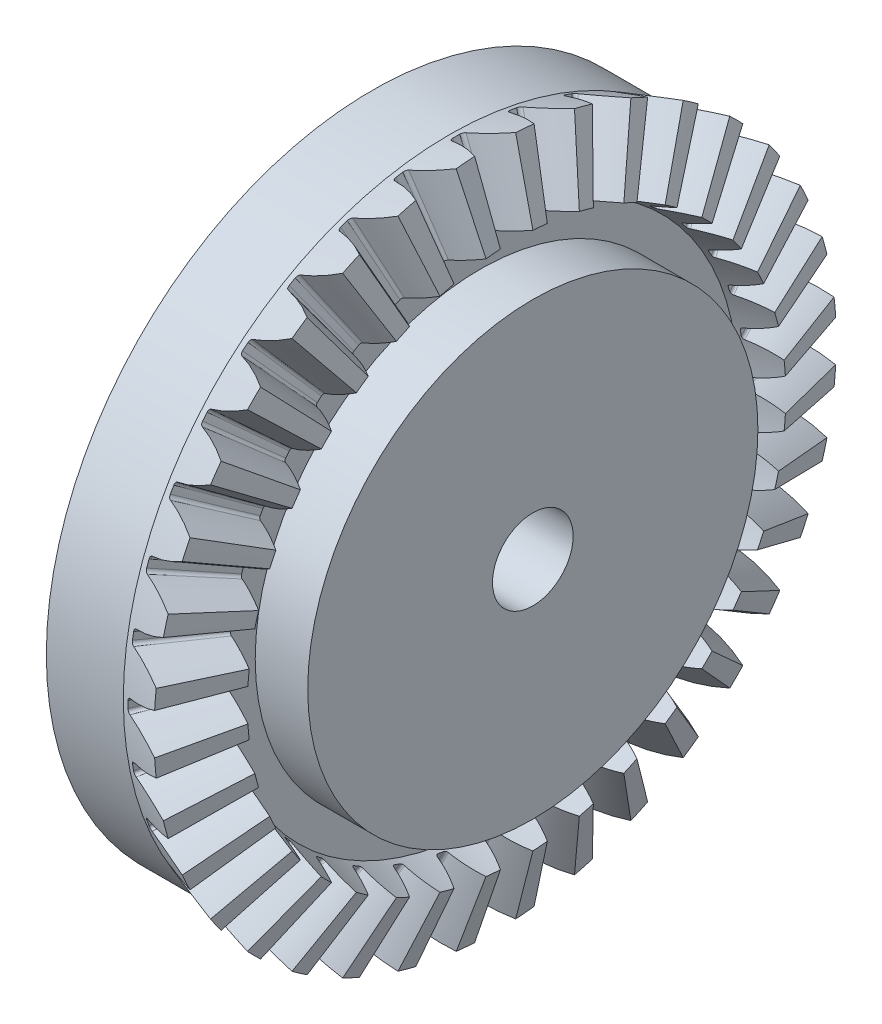
SolidWorks part; units mm, degrees
revolve "Base-Revolve" add sketch "BasProSke" angle 360 about L0 other way angle 5
sketch "BasProSke" plane through (0, 0, 0) normal (0, 1, 0) x (1, 0, 0)
  line L0 (-10, 0) -> (60, 0) construction
  line L1 (0, 0) -> (0, 8.684)
  line L2 (0, 0) -> (0.8323, 0)
  line L3 (0.8323, 0) -> (0.8323, 6.8532)
  line L4 (3.948, 0) -> (-9.0794, 39.0823) construction
  line L5 (0, 8.684) -> (1.2284, 9.0935)
  line L6 (3.948, 0) -> (-23.6442, 92.2592) construction
  line L7 (3.948, 0) -> (0, 8.684) construction
  line L8 (1.2284, 9.0935) -> (1.8018, 7.1764)
  line L9 (1.8018, 7.1764) -> (0.8323, 6.8532)
  line L10 (0.948, 9) -> (-11.0363, 9) construction
  dimension "D1" = 17.368
  dimension "D2" = 3.948
  dimension "D3" = 9.4868
  dimension "D4" = 1.784
ref_plane "Plane1" through (0, 0, 0) normal (0, 0, 1) x (1, 0, 0)
ref_plane "Plane2" through (0, 0, 0) normal (0, 1, 0) x (1, 0, 0)
ref_plane "Plane3" through (0, 0, 0) normal (1, 0, 0) x (0, 0, -1)
other "Configuration Table"
sketch "HoldingSke" plane through (0, 0, 0) normal (0, 1, 0) x (1, 0, 0)
  line L0 (0, 0) -> (1.618, -1.1756)
  line L1 (-15, 0) -> (100, 0) construction
  line L2 (0, 0) -> (-122.6628, 25.2748)
  line L3 (0, 0) -> (-11.863, 4.5341)
  line L4 (0, 0) -> (6.9867, 5.0761)
  line L5 (0, 0) -> (-5.6217, -2.0967)
  line L6 (0, 0) -> (-10.5278, -7.1032)
  line L7 (-122.6628, 25.2748) -> (-122.6177, 31.2747)
  line L8 (-76.2, 0.5) -> (-75.9, 0.5)
  line L9 (-71.009, 38.7566) -> (-53.1078, 45.2721)
  line L10 (-76.2, 71.12) -> (104.1128, 71.12)
  line L11 (0, 0) -> (-2, 0)
  line L12 (-76.2, 101.6) -> (-76.181, 101.6)
  line L13 (24.9733, 27.94) -> (52.9546, 28.2287)
  line L14 (24.9733, 27.94) -> (24.9743, 27.94)
  line L15 (24.9733, 27.94) -> (100.3893, 30.0425)
  line L16 (-122.6628, 25.2748) -> (3.6233, -1.5681)
  circle A0 centre (0, 0) radius 1
  circle A1 centre (0, 0) radius 8.684
  circle A2 centre (0, 0) radius 10
  circle A3 centre (0, 0) radius 1
  dimension "Num_teeth" = 36
  dimension "Pitch_radius" = 180.3128
  dimension "Width" = 2
ref_plane "ToothPln" through (0.6142, 8.8887, 0) normal (-0.3162, 0.9487, 0) x (0, 0, -1)
ref_plane "ToothPln2" through (0.3948, -1.1844, 0) normal (-0.3162, 0.9487, 0) x (0, 0, 1)
sketch "TooCutSke" plane through (0.6142, 8.8887, 0) normal (-0.3162, 0.9487, 0) x (0, 0, -1)
  line L2 (0, 8.6481) -> (144.0891, -1638.2981) construction
  line L3 (0, 8.6481) -> (78.8921, -1755.5054) construction
  line L4 (0, -15.621) -> (0, 105.791) construction
  line L6 (-24.765, -0.6474) -> (21.082, -0.6474) construction
  line L7 (0.7844, -0.3176) -> (0.4017, -0.3347) construction
  arc A0 (-0.6442, -0.8114) -> (0.6442, -0.8114) centre (0, 8.6481) ccw
  arc A1 (-0.094, 0.4481) -> (0.094, 0.4481) centre (0, 8.6481) ccw
  circle A2 centre (0, 8.6481) radius 9 construction
  circle A3 centre (0, 8.6481) radius 8.4572 construction
  arc A4 (0.1883, 0.3711) -> (0.094, 0.4481) centre (0.0951, 0.3531) ccw
  arc A5 (0.1883, 0.3711) -> (0.6442, -0.8114) centre (3.7229, 1.0544) ccw
  arc A6 (-0.6442, -0.8114) -> (-0.1883, 0.3711) centre (-3.7229, 1.0544) ccw
  arc A7 (-0.094, 0.4481) -> (-0.1883, 0.3711) centre (-0.0951, 0.3531) ccw
  ellipse E0 centre (0, 2.2282) end of major axis (9.0935, 2.2282) minor radius 2.8756 construction
sketch "TooCutSke2" plane through (0.3948, -1.1844, 0) normal (-0.3162, 0.9487, 0) x (0, 0, 1)
  line L0 (0, 0) -> (0, 68.072) construction
  line L2 (21.082, 2.7461) -> (-20.32, 2.7461) construction
  circle A0 centre (0, 3.7454) radius 0.0127
  ellipse E1 centre (0, 0) end of major axis (-8.684, 0) minor radius 2.7461 construction
loft "ToothCut" cut profiles "TooCutSke2", "TooCutSke"
pattern_circular "TeethCuts" count 36 every 10 about axis through (-10, 0, 0) along (1, 0, 0) of "ToothCut"
sketch "草图1" plane through (0.8323, 0, 0) normal (1, 0, 0) x (0, 0, -1)
  circle A0 centre (0, 0) radius 6
  dimension "D1" = 12
extrude "凸台-拉伸1" add sketch "草图1" along normal blind 1.4
sketch "HubSke" plane through (0, 0, 0) normal (-1, 0, 0) x (0, 0, 1)
  circle A0 centre (0, 0) radius 8.684
  dimension "Diameter" = 17.368
extrude "Hub" add sketch "HubSke" along normal blind 2.0521
sketch "BorSke" plane through (0, 0, 0) normal (1, 0, 0) x (0, 0, -1)
  circle A0 centre (0, 0) radius 1.075
  dimension "Diameter" = 2.15
extrude "Bore" cut sketch "BorSke" along normal mid plane 12.0001
sketch "KeySke" plane through (0, 0, 0) normal (1, 0, 0) x (0, 0, -1)
  line L0 (-0.4, 0) -> (-0.4, 1.3)
  line L1 (-0.4, 1.3) -> (0.4, 1.3)
  line L2 (0.4, 1.3) -> (0.4, 0)
  line L3 (0, 0) -> (0, 34) construction
  line L4 (-0.4, 0) -> (0.4, 0)
  dimension "Offset" = 1.3
extrude "Keyway" [suppressed] cut sketch "KeySke" along normal mid plane 12.0001
pattern_circular "Keyway2" [suppressed] count 2 every 90 about axis through (-10, 0, 0) along (1, 0, 0) reverse direction yes
equation "' \"Module@HoldingSke\" = 6.35"
equation "' \"Num_teeth@HoldingSke\" = 20"
equation "' \"Mating_teeth@HoldingSke\" = 12"
equation "' \"Ap@HoldingSke\" =  20"
equation "' \"Ap@HoldingSke\" = 20"
equation "' \"Width@HoldingSke\" = 0.5 * 25.4"
equation "' \"Hub_dia@HoldingSke\"= 2 * 25.4"
equation "' \"Hub_dia@HoldingSke\" = 2 * 25.4"
equation "' \"Mounting_dist@HoldingSke\" = 3 * 25.4"
equation "' \"Bore@HoldingSke\" = 19"
equation "' \"T_dim@HoldingSke\" = 0.1 * 25.4"
equation "' \"Width@KeySke\" = 0.25 * 25.4"
equation "' \"Show_teeth@HoldingSke\" = 100"
equation "' \"Backlash@HoldingSke\" = 0.009 * 25.4"
equation "' \"Addendum_fac@HoldingSke\" = 1.0"
equation "' \"Dedendum_fac@HoldingSke\" = 1.188"
equation "' \"Dedendum_add@HoldingSke\" = 0.002 * 25.4"
equation "' \"Clearance_fac@HoldingSke\" = 0.188"
equation "\"Pitch@HoldingSke\" = 1 / \"Module@HoldingSke\""
equation " \"Addendum_fac@HoldingSke\" = 0.54 + 0.46 / (\"Num_teeth@HoldingSke\" /  \"Mating_teeth@HoldingSke\" ) ^ 2"
equation "' \"Addendum_fac@HoldingSke\" = 2 - (0.54 + 0.46 / (\"Mating_teeth@HoldingSke\" /  \"Num_teeth@HoldingSke\" ) ^ 2)"
equation "\"Dedendum_fac@HoldingSke\" = 2.188 - \"Addendum_fac@HoldingSke\""
equation "\"Pitch_rad@BasProSke\" = \"Num_teeth@HoldingSke\" / \"Pitch@HoldingSke\" / 2"
equation "\"Pitch_ang@BasProSke\" = atn(\"Num_teeth@HoldingSke\" / \"Mating_teeth@HoldingSke\") * (180 / 3.14159265)"
equation "\"Addendum@BasProSke\" = \"Addendum_fac@HoldingSke\" / \"Pitch@HoldingSke\""
equation "\"Dedendum_plus@BasProSke\" = (\"Dedendum_fac@HoldingSke\" / \"Pitch@HoldingSke\" + \"Dedendum_add@HoldingSke\") * 1.25"
equation "\"Face_wid@BasProSke\" = \"Width@HoldingSke\""
equation "\"Radius@TooCutSke\" = ((\"Num_teeth@HoldingSke\" + 2 * \"Addendum_fac@HoldingSke\") / \"Pitch@HoldingSke\" ) / 2"
equation "\"Overcut_dia@TooCutSke\" =  1.02 * (\"Num_teeth@HoldingSke\" + 2 * \"Addendum_fac@HoldingSke\") / \"Pitch@HoldingSke\""
equation "\"Pitch_dia@TooCutSke\" = \"Num_teeth@HoldingSke\" / \"Pitch@HoldingSke\""
equation "\"Base_dia@TooCutSke\" = \"Num_teeth@HoldingSke\" / \"Pitch@HoldingSke\" * cos((\"Ap@HoldingSke\"  * 3.14159265 / 180))"
equation "'  \"Root_dia@TooCutSke\" =  (\"Num_teeth@HoldingSke\" + 2) / \"Pitch@HoldingSke\" - 2 * (\"Addendum_fac@HoldingSke\" + \"Dedendum_fac@HoldingSke\") / \"Pitch@HoldingSke\" - \"Dedendum_add@HoldingSke\" * 2"
equation "'  \"Root_dia@TooCutSke\" = (\"Num_teeth@HoldingSke\" + 2) / \"Pitch@HoldingSke\" - 2 * (\"Addendum_fac@HoldingSke\" + \"Dedendum_fac@HoldingSke\") / \"Pitch@HoldingSke\" - \"Dedendum_add@HoldingSke\" * 2"
equation "\"Root_dia@TooCutSke\" =  \"Num_teeth@HoldingSke\" / \"Pitch@HoldingSke\" -  2 * \"Dedendum_fac@HoldingSke\" / \"Pitch@HoldingSke\" - \"Dedendum_add@HoldingSke\" * 2"
equation "\"Half_ang@TooCutSke\" = 180 / \"Num_teeth@HoldingSke\""
equation "\"Half_CT@TooCutSke\" = \"Num_teeth@HoldingSke\" / \"Pitch@HoldingSke\" * sin((3.14159265 / 2 / \"Num_teeth@HoldingSke\")) / 2 - 2 * \"Backlash@HoldingSke\" / 4"
equation "\"Flank_rad@TooCutSke\" = \"Num_teeth@HoldingSke\" / \"Pitch@HoldingSke\" / 5"
equation "\"Root_fillet@TooCutSke\" = \"Clearance_fac@HoldingSke\" / \"Pitch@HoldingSke\" + \"Dedendum_add@HoldingSke\""
equation "\"Offset@ToothPln2\"  = \"Num_teeth@HoldingSke\" / \"Pitch@HoldingSke\" / 2 / sin(atn(\"Num_teeth@HoldingSke\" / \"Mating_teeth@HoldingSke\"))"
equation "\"Dedendum_plus@TooCutSke2\" = \"Dedendum_plus@BasProSke\""
equation "\"MHD@HoldingSke\" = \"Num_teeth@HoldingSke\" / \"Pitch@HoldingSke\" - 2 * \"Dedendum_plus@BasProSke\" * cos(atn(\"Num_teeth@HoldingSke\" / \"Mating_teeth@HoldingSke\"))"
equation "\"MBD@HoldingSke\" = \"Num_teeth@HoldingSke\" / \"Pitch@HoldingSke\" - 2 * \"Dedendum_plus@BasProSke\" * cos(atn(\"Num_teeth@HoldingSke\" / \"Mating_teeth@HoldingSke\")) - 0.002 * 25.4"
equation "\"MnMD@HoldingSke\" =  \"Num_teeth@HoldingSke\" / \"Pitch@HoldingSke\" / 2 / (\"Num_teeth@HoldingSke\" / \"Mating_teeth@HoldingSke\") + \"Dedendum_plus@BasProSke\" * sin(atn(\"Num_teeth@HoldingSke\" / \"Mating_teeth@HoldingSke\"))"
equation "\"OAL@HoldingSke\" = \"MnMD@HoldingSke\""
equation "\"MHD@HoldingSke\" = ((sgn( \"MHD@HoldingSke\" - \"Hub_dia@HoldingSke\" )-1)*( \"MHD@HoldingSke\" - \"Hub_dia@HoldingSke\" ))/-2+ \"Hub_dia@HoldingSke\""
equation "\"MBD@HoldingSke\" = ((sgn( \"MBD@HoldingSke\" - \"Bore@HoldingSke\" )-1)*( \"MBD@HoldingSke\" - \"Bore@HoldingSke\" ))/-2+ \"Bore@HoldingSke\""
equation "\"Face_wid@BasProSke\" = ((sgn( \"Face_wid@BasProSke\" - \"Offset@ToothPln2\" * 0.9)-1)*( \"Face_wid@BasProSke\" - \"Offset@ToothPln2\" * 0.9))/-2+ \"Offset@ToothPln2\" * 0.9"
equation "\"OAL@HoldingSke\" = ((sgn( \"OAL@HoldingSke\" - \"Mounting_dist@HoldingSke\" )+1)*( \"OAL@HoldingSke\" - \"Mounting_dist@HoldingSke\" ))/2 + \"Mounting_dist@HoldingSke\" + 0.000002 * 25.4"
equation "\"Num_teeth@TeethCuts\" = int( \"Show_teeth@HoldingSke\" ) + 1"
equation "\"Num_teeth@TeethCuts\" = ((sgn( \"Num_teeth@TeethCuts\" - \"Num_teeth@HoldingSke\" )-1)*( \"Num_teeth@TeethCuts\" - \"Num_teeth@HoldingSke\" ))/-2+ \"Num_teeth@HoldingSke\""
equation "\"Num_teeth@TeethCuts\" = ((sgn( \"Num_teeth@TeethCuts\" - 2.0)+1)*( \"Num_teeth@TeethCuts\" - 2.0))/2 +2.0"
equation "\"Angle@TeethCuts\" = 360.0 / \"Num_teeth@HoldingSke\""
equation "\"Diameter@HubSke\" = \"MHD@HoldingSke\""
equation "\"Length@Hub\" = \"OAL@HoldingSke\" - \"MnMD@HoldingSke\" + 0.000002 * 25.4"
equation "\"D1@Bore\" = \"OAL@HoldingSke\" * 2.0"
equation "\"D1@Keyway\" = \"OAL@HoldingSke\" * 2.0"
equation "\"Offset@KeySke\" = \"T_dim@HoldingSke\" + \"MBD@HoldingSke\" / 2.0"
